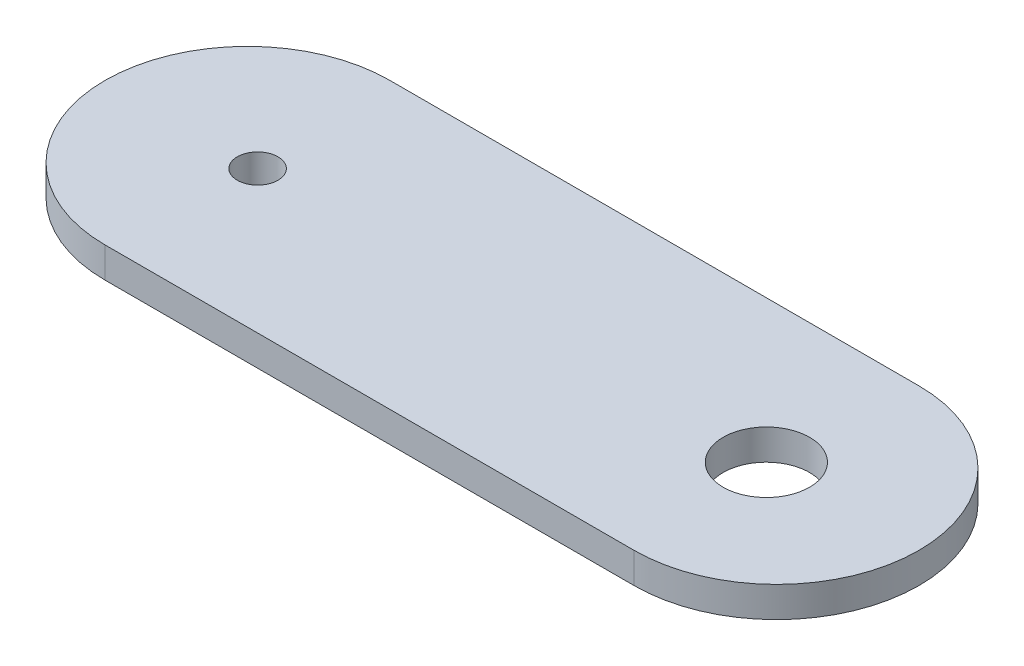
SolidWorks part; units mm, degrees
ref_plane "前视" through (0, 0, 0) normal (0, 0, 1) x (1, 0, 0)
ref_plane "上视" through (0, 0, 0) normal (0, 1, 0) x (1, 0, 0)
ref_plane "右视" through (0, 0, 0) normal (1, 0, 0) x (0, 0, -1)
sketch "草图1" plane through (0, 0, 0) normal (0, 1, 0) x (1, 0, 0)
  line L1 (-40, 14) -> (40, 14)
  line L2 (-40, 14) -> (-40, -14)
  line L3 (-40, -14) -> (40, -14)
  line L4 (40, 14) -> (40, -14)
  line L5 (-40, 14) -> (40, -14) construction
  line L6 (-40, -14) -> (40, 14) construction
  circle A0 centre (25, 0) radius 4.25
  circle A1 centre (-25, 0) radius 2
  point P0 (0, 0)
  dimension "D3" = 4
  dimension "D4" = 8.5
  dimension "D1" = 80
  dimension "D2" = 28
  dimension "D5" = 50
  dimension "D6" = 25
extrude "凸台-拉伸1" add sketch "草图1" along normal blind 3
sketch "草图2" plane through (0, 3, 0) normal (0, 1, 0) x (1, 0, 0)
  text T0 "        <b>     1</b>"
extrude "凸台-拉伸2" [suppressed] add sketch "草图2" along normal blind 0.5
fillet "圆角1" 2 edges at (-40, 1.5, -14) (-40, 1.5, 14) type full round first side face at (0, 1.5, -14) second side face at (0, 1.5, 14) middle face at (-40, 1.5, 0)
fillet "圆角2" 2 edges at (40, 1.5, -14) (40, 1.5, 14) type full round first side face at (7, 1.5, -14) second side face at (7, 1.5, 14) middle face at (40, 1.5, 0)
